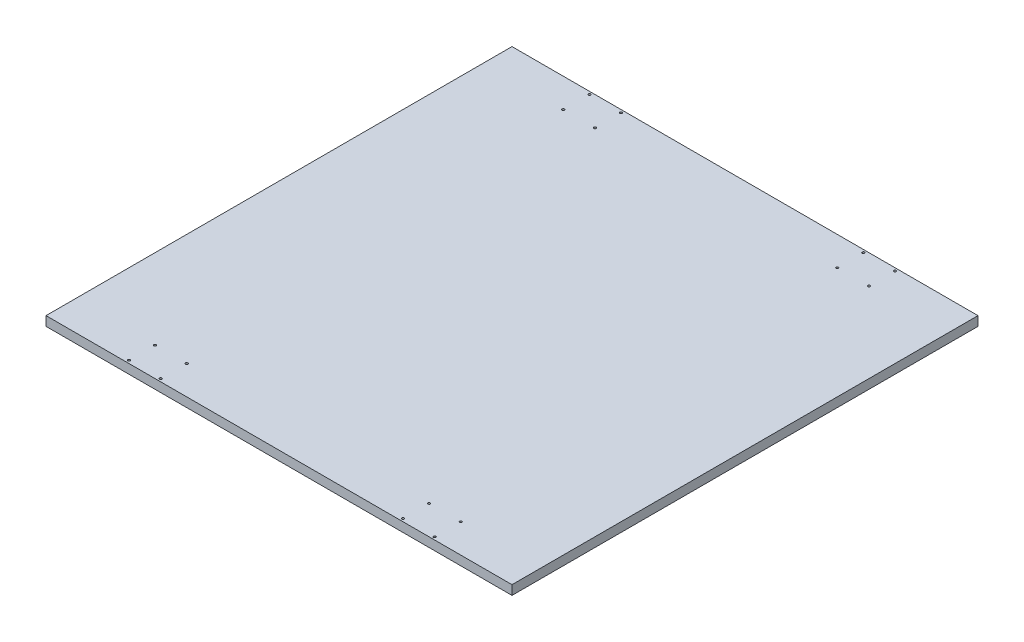
SolidWorks part; units mm, degrees
material "AISI 1045 Steel, cold drawn"
ref_plane "Front Plane" through (0, 0, 0) normal (0, 0, 1) x (1, 0, 0)
ref_plane "Top Plane" through (0, 0, 0) normal (0, 1, 0) x (1, 0, 0)
ref_plane "Right Plane" through (0, 0, 0) normal (1, 0, 0) x (0, 0, -1)
sketch "Sketch1" plane through (0, 0, 0) normal (0, 1, 0) x (1, 0, 0)
  line L1 (250, -250) -> (-250, -250)
  line L2 (250, -250) -> (250, 250)
  line L3 (250, 250) -> (-250, 250)
  line L4 (-250, -250) -> (-250, 250)
  line L5 (250, -250) -> (-250, 250) construction
  line L6 (250, 250) -> (-250, -250) construction
  point P0 (0, 0)
  dimension "D1" = 500
extrude "Boss-Extrude1" add sketch "Sketch1" along normal blind 10
sketch "Sketch2" plane through (0, 10, 0) normal (0, 1, 0) x (1, 0, 0)
  line L0 (250, -250) -> (250, 250) construction
  line L1 (164, -247) -> (130, -247)
  line L2 (164, -247) -> (164, -219)
  line L3 (164, -219) -> (130, -219)
  line L4 (130, -247) -> (130, -219)
  line L5 (-250, -250) -> (250, -250) construction
  line L6 (0, -1000) -> (0, 49000) construction
  line L7 (-130, -247) -> (-130, -219)
  line L8 (-164, -219) -> (-130, -219)
  line L9 (-164, -247) -> (-164, -219)
  line L10 (-164, -247) -> (-130, -247)
  line L11 (-1000, 0) -> (49000, 0) construction
  line L12 (-164, 247) -> (-130, 247)
  line L13 (-164, 247) -> (-164, 219)
  line L14 (-164, 219) -> (-130, 219)
  line L15 (-130, 247) -> (-130, 219)
  line L16 (130, 247) -> (130, 219)
  line L17 (164, 219) -> (130, 219)
  line L18 (164, 247) -> (164, 219)
  line L19 (164, 247) -> (130, 247)
  dimension "D1" = 86
  dimension "D2" = 34
  dimension "D3" = 28
  dimension "D4" = 3
hole_wizard "Tap Drill for M3x0.5 Tap1" positions "Sketch3" profile "Sketch4" hole size "M3x0.5" standard "ANSI Metric" end condition through all
sketch "Sketch3" plane through (0, 10, 0) normal (0, 1, 0) x (1, 0, 0)
  point P0 (164, -219)
  point P3 (164, -247)
  point P6 (130, -247)
  point P9 (130, -219)
  point P12 (-130, -219)
  point P15 (-164, -219)
  point P18 (-164, -247)
  point P21 (-130, -247)
  point P24 (-130, 219)
  point P27 (-130, 247)
  point P30 (-164, 247)
  point P33 (-164, 219)
  point P36 (130, 247)
  point P39 (164, 247)
  point P42 (164, 219)
  point P45 (130, 219)
sketch "Sketch4" plane through (164, 10, 219) normal (1, 0, 0) x (0, 0, 1)
  line L0 (0, 0) -> (0, 10)
  line L1 (0, 10) -> (1.25, 10)
  line L2 (1.25, 10) -> (1.25, 0)
  line L5 (1.25, 0) -> (0, 0)
  line L11 (0, -6.35) -> (0, 107.95) construction
  dimension "Thru Hole Dia." = 2.5
  dimension "Thru Hole Depth" = 10
